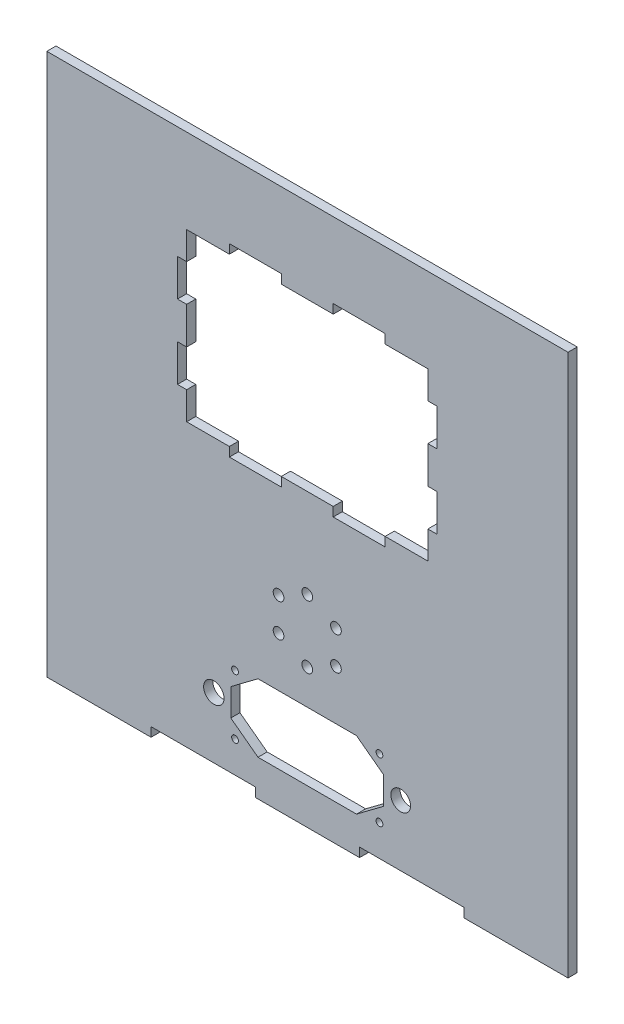
SolidWorks part; units mm, degrees
ref_plane "Ön Düzlem" through (0, 0, 0) normal (0, 0, 1) x (1, 0, 0)
ref_plane "Üst Düzlem" through (0, 0, 0) normal (0, 1, 0) x (1, 0, 0)
ref_plane "Sağ Düzlem" through (0, 0, 0) normal (1, 0, 0) x (0, 0, -1)
sketch "Sketch1" plane through (0, 0, 0) normal (0, 0, 1) x (1, 0, 0)
  line L21 (-45.9723, -28.1459) -> (-45.9723, -25.4459)
  line L22 (-15.2923, -28.1459) -> (-15.2923, -25.4459)
  line L23 (15.3877, -28.1459) -> (15.3877, -25.4459)
  line L24 (46.0677, -28.1459) -> (46.0677, -25.4459)
  line L26 (-76.6523, -23.1459) -> (-76.6523, 12.8541)
  line L27 (-76.6523, -23.1459) -> (-76.6523, -25.4459)
  line L28 (76.7477, -23.1459) -> (76.7477, 12.8541)
  line L30 (76.7477, -25.4459) -> (76.7477, -23.1459)
  line L33 (-45.9723, -28.1459) -> (-76.6523, -28.1459)
  line L34 (-76.6523, -28.1459) -> (-76.6523, -25.4459)
  line L35 (-15.2923, -25.4459) -> (-45.9723, -25.4459)
  line L36 (-15.2923, -28.1459) -> (15.3877, -28.1459)
  line L37 (15.3877, -25.4459) -> (46.0677, -25.4459)
  line L38 (46.0677, -28.1459) -> (76.7477, -28.1459)
  line L39 (76.7477, -28.1459) -> (76.7477, -25.4459)
  line L56 (-22.5, -3.5) -> (-14.5, 2.5)
  line L57 (-14.5, 2.5) -> (14.5, 2.5)
  line L58 (0, -17.5) -> (14.5, -17.5)
  line L59 (-14.5, -17.5) -> (-22.5, -11.5)
  line L60 (-22.5, -11.5) -> (-22.5, -3.5)
  line L61 (14.5, -17.5) -> (22.5, -11.5)
  line L62 (14.5, 2.5) -> (22.5, -3.5)
  line L63 (0, -17.5) -> (-14.5, -17.5)
  line L64 (22.5, -3.5) -> (22.5, -11.5)
  line L65 (35.5, 57.5) -> (22.92, 57.5)
  line L66 (35.5, 57.5) -> (35.5, 65.68)
  line L67 (35.5, 106.5) -> (22.92, 106.5)
  line L68 (-35.5, 57.5) -> (-35.5, 65.68)
  line L80 (76.7477, 12.8541) -> (76.7477, 131.3541)
  line L81 (-76.6523, 131.3541) -> (-76.6523, 12.8541)
  line L82 (76.7477, 131.3541) -> (-76.6523, 131.3541)
  line L84 (-22.92, 54.8) -> (-7.64, 54.8)
  line L85 (-22.92, 109.2) -> (-7.64, 109.2)
  line L88 (38.2, 65.68) -> (38.2, 76.56)
  line L89 (7.64, 109.2) -> (22.92, 109.2)
  line L91 (-38.2, 65.68) -> (-38.2, 76.56)
  line L93 (-38.2, 87.44) -> (-38.2, 98.32)
  line L95 (-38.2, 98.32) -> (-35.5, 98.32)
  line L96 (-38.2, 87.44) -> (-35.5, 87.44)
  line L97 (-38.2, 76.56) -> (-35.5, 76.56)
  line L98 (-38.2, 65.68) -> (-35.5, 65.68)
  line L99 (35.5, 65.68) -> (38.2, 65.68)
  line L100 (35.5, 76.56) -> (38.2, 76.56)
  line L101 (35.5, 87.44) -> (38.2, 87.44)
  line L102 (35.5, 98.32) -> (38.2, 98.32)
  line L103 (-22.92, 109.2) -> (-22.92, 106.5)
  line L104 (-7.64, 109.2) -> (-7.64, 106.5)
  line L105 (7.64, 109.2) -> (7.64, 106.5)
  line L106 (22.92, 109.2) -> (22.92, 106.5)
  line L107 (-22.92, 57.5) -> (-22.92, 54.8)
  line L108 (-7.64, 57.5) -> (-7.64, 54.8)
  line L109 (7.64, 57.5) -> (7.64, 54.8)
  line L110 (22.92, 57.5) -> (22.92, 54.8)
  line L111 (-22.92, 106.5) -> (-35.5, 106.5)
  line L112 (7.64, 106.5) -> (-7.64, 106.5)
  line L113 (35.5, 98.32) -> (35.5, 106.5)
  line L114 (35.5, 76.56) -> (35.5, 87.44)
  line L115 (7.64, 57.5) -> (-7.64, 57.5)
  line L116 (-22.92, 57.5) -> (-35.5, 57.5)
  line L117 (-35.5, 76.56) -> (-35.5, 87.44)
  line L118 (-35.5, 98.32) -> (-35.5, 106.5)
  line L119 (38.2, 87.44) -> (38.2, 98.32)
  line L120 (7.64, 54.8) -> (22.92, 54.8)
  circle A11 centre (-21.25, -16.25) radius 1
  circle A12 centre (-27.5, -7.5) radius 3
  circle A13 centre (-21.25, 1.25) radius 1
  circle A14 centre (21.25, -16.25) radius 1
  circle A15 centre (27.5, -7.5) radius 2.9
  circle A16 centre (21.25, 1.25) radius 1
  circle A17 centre (0, 31.25) radius 1.575
  circle A18 centre (0, 12.75) radius 1.575
  circle A19 centre (-8.4437, 17.125) radius 1.575
  circle A20 centre (-8.4437, 26.875) radius 1.575
  circle A21 centre (8.4437, 26.875) radius 1.575
  circle A22 centre (8.4437, 17.125) radius 1.575
  point P0 (0, 82)
  point P39 (0, 31.25)
  point P80 (0, 0)
  point P82 (0, 12.75)
extrude "Boss-Extrude3" add sketch "Sketch1" along normal blind 2.7
